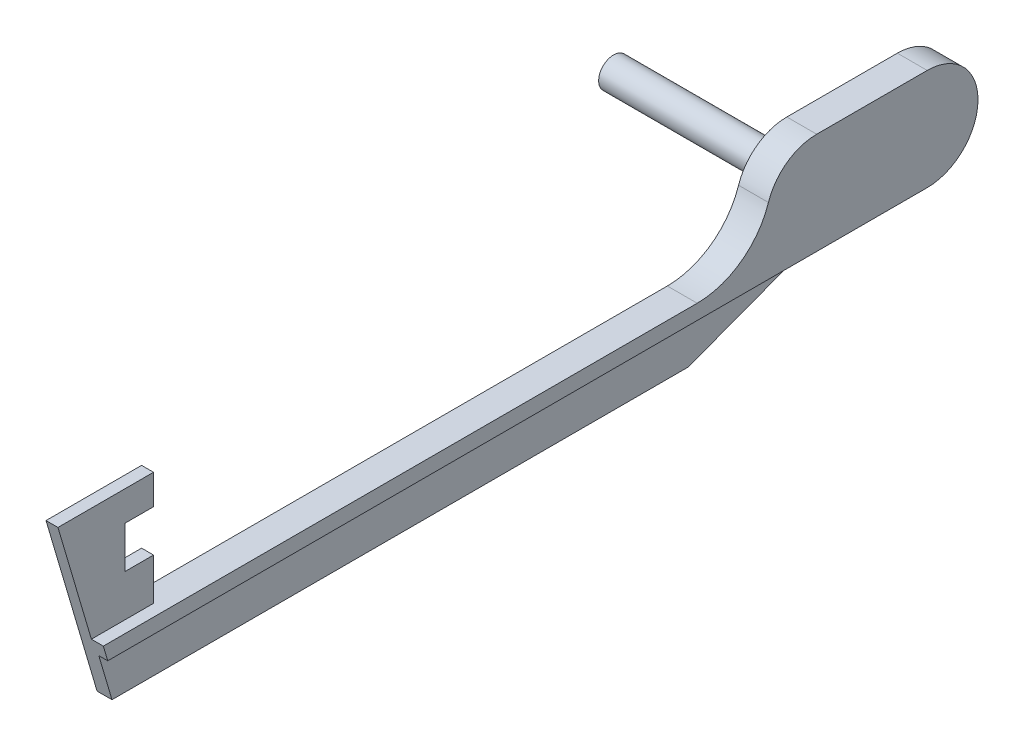
SolidWorks part; units mm, degrees
material "Plain Carbon Steel"
ref_plane "Front Plane" through (0, 0, 0) normal (0, 0, 1) x (1, 0, 0)
ref_plane "Top Plane" through (0, 0, 0) normal (0, 1, 0) x (1, 0, 0)
ref_plane "Right Plane" through (0, 0, 0) normal (1, 0, 0) x (0, 0, -1)
sketch "Sketch1" plane through (0, 0, 0) normal (1, 0, 0) x (0, 0, -1)
  line L0 (0, 4.318) -> (0, -4.318)
  line L1 (0, 4.318) -> (-9.398, 4.318)
  line L2 (0, -4.318) -> (-9.398, -4.318)
  line L3 (-9.398, 4.318) -> (-9.398, -4.318)
  line L4 (-19.558, -3.048) -> (-19.558, -8.128)
  line L5 (-19.558, -3.048) -> (-64.77, -3.048)
  line L6 (-19.558, -8.128) -> (-64.77, -8.128)
  line L7 (-64.77, -3.048) -> (-64.77, -8.128)
  line L8 (-9.398, -4.318) -> (-19.558, -8.128)
  line L9 (-64.77, -3.048) -> (-64.77, 0.508)
  line L10 (-64.77, 0.508) -> (-67.2005, 0.508)
  line L11 (-67.2005, 0.508) -> (-67.2005, 4.064)
  line L12 (-67.2005, 4.064) -> (-64.77, 4.064)
  line L13 (-64.77, 4.064) -> (-64.77, 6.604)
  line L14 (-64.77, 6.604) -> (-72.898, 6.604)
  line L15 (-64.77, -8.128) -> (-68.5565, -8.128)
  line L16 (-72.898, 6.604) -> (-68.5565, -8.128)
  line L17 (-64.77, -3.048) -> (-70.0536, -3.048)
  line L18 (-9.398, -4.318) -> (-69.6793, -4.318)
  circle A0 centre (0, 0) radius 4.318
  circle A2 centre (-9.144, 0) radius 1.27
  arc A4 (-9.398, 4.318) -> (-13.502, 1.3426) centre (-9.398, 0) ccw
  arc A5 (-13.502, 1.3426) -> (-19.558, -3.048) centre (-19.558, 3.3239) cw
  arc A6 (-9.398, 4.318) -> (-13.502, 1.3426) centre (-9.398, 0) ccw
  dimension "D1" = 8.636
  dimension "D3" = 10.16
  dimension "D4" = 1.27
  dimension "D13" = 2.54
  dimension "D2" = 9.398
  dimension "D5" = 45.212
  dimension "D6" = 5.08
  dimension "D7" = 3.556
  dimension "D8" = 3.556
  dimension "D9" = 2.4305
  dimension "D10" = 2.54
  dimension "D11" = 3.7865
  dimension "D12" = 8.128
  dimension "D14" = 9.144
  dimension "D15" = 4.318
extrude "Boss-Extrude2" add sketch "Sketch1" along normal blind 2.54 contours L0 A0 | L0 A0 | A2 L3 L2 A0 L1 | A4 A5 L4 L18 L3 A2 | L18 L4 L5 L7 | L18 L7 L17 L16 | L3 A2 | L3 A2 region at (0, 0, -1.8326) region at (0, 0, 6.1595) region at (0, 0, 1.8326) region at (0, -1.1798, 12.8483) region at (0, 0, 8.7394) region at (0, 0, 9.8226) region at (0, -3.683, 42.164) region at (0, -3.6752, 67.3194)
extrude "Boss-Extrude3" add sketch "Sketch1<5>" along normal blind 1.778 contours L8 L18 L4 | L4 L18 L7 L6 | L7 L18 L16 L15 region at (0, -5.588, 16.1713) region at (0, -6.223, 42.164) region at (0, -6.141, 66.956)
sketch "Sketch1<5>" plane through (0, 0, 0) normal (1, 0, 0) x (0, 0, -1) same geometry as "Sketch1"
extrude "Boss-Extrude4" add sketch "Sketch1<7>" against normal blind 1.27 from offset 1.524 contours L17 L9 L10 L11 L12 L13 L14 L16 region at (0, 2.0935, 68.5104)
sketch "Sketch1<7>" plane through (0, 0, 0) normal (1, 0, 0) x (0, 0, -1) same geometry as "Sketch1"
extrude "Boss-Extrude5" add sketch "Sketch1<8>" against normal blind 14.986 contours L3 A2 | L3 A2 region at (0, 0, 8.7394) region at (0, 0, 9.8226)
sketch "Sketch1<8>" plane through (0, 0, 0) normal (1, 0, 0) x (0, 0, -1) same geometry as "Sketch1"
sketch "Sketch2" plane through (0, 6.604, 0) normal (0, 1, 0) x (1, 0, 0)
  line L0 (0.254, -72.898) -> (1.524, -72.898) construction
  line L1 (0.508, -72.898) -> (0, -72.898)
  line L2 (0.508, -72.898) -> (0.508, -64.77)
  line L3 (0.508, -64.77) -> (0, -64.77)
  line L4 (0, -72.898) -> (0, -64.77)
  line L5 (0, -19.558) -> (0, -70.0536) construction
  line L6 (0.254, -64.77) -> (1.524, -64.77) construction
  dimension "D1" = 0.508
extrude "Cut-Extrude1" cut sketch "Sketch2" against normal through all
